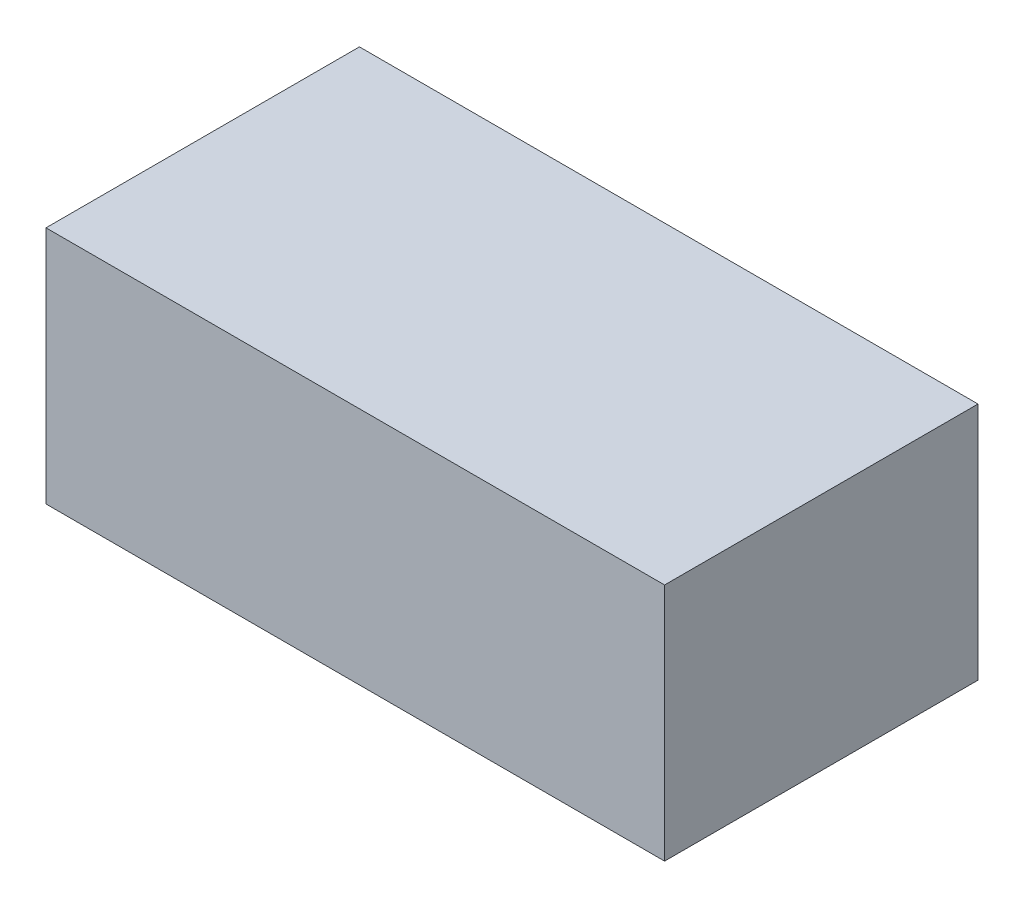
SolidWorks part; units mm, degrees
ref_plane "Front Plane" through (0, 0, 0) normal (0, 0, 1) x (1, 0, 0)
ref_plane "Top Plane" through (0, 0, 0) normal (0, 1, 0) x (1, 0, 0)
ref_plane "Right Plane" through (0, 0, 0) normal (1, 0, 0) x (0, 0, -1)
sketch "Sketch1" plane through (0, 0, 0) normal (0, 1, 0) x (1, 0, 0)
  line L1 (-37.5, 19) -> (37.5, 19)
  line L2 (-37.5, 19) -> (-37.5, -19)
  line L3 (-37.5, -19) -> (37.5, -19)
  line L4 (37.5, 19) -> (37.5, -19)
  line L5 (-37.5, 19) -> (37.5, -19) construction
  line L6 (-37.5, -19) -> (37.5, 19) construction
  point P0 (0, 0)
  dimension "D1" = 38
  dimension "D2" = 75
extrude "Boss-Extrude1" add sketch "Sketch1" along normal blind 29
sketch "Sketch2" plane through (-37.5, 0, 0) normal (-1, 0, 0) x (0, 0, 1)
  line L1 (-7.0532, 30.4622) -> (7.0532, 30.4622)
  line L2 (-7.0532, 30.4622) -> (-7.0532, 16.5378)
  line L3 (-7.0532, 16.5378) -> (7.0532, 16.5378)
  line L4 (7.0532, 30.4622) -> (7.0532, 16.5378)
  line L5 (-7.0532, 30.4622) -> (7.0532, 16.5378) construction
  line L6 (-7.0532, 16.5378) -> (7.0532, 30.4622) construction
  point P0 (0, 23.5)
